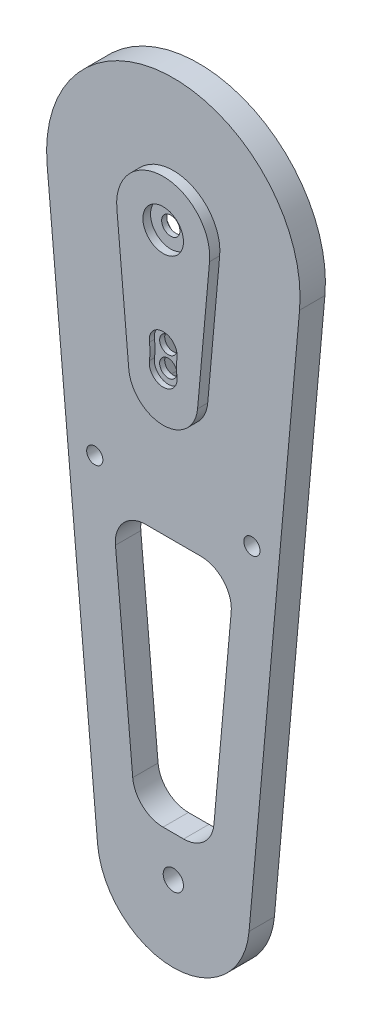
SolidWorks part; units mm, degrees
material "PLA"
ref_plane "Alzado" through (0, 0, 0) normal (0, 0, 1) x (1, 0, 0)
ref_plane "Planta" through (0, 0, 0) normal (0, 1, 0) x (1, 0, 0)
ref_plane "Vista lateral" through (0, 0, 0) normal (1, 0, 0) x (0, 0, -1)
other "PLA"
sketch "Croquis1" plane through (0, 0, 0) normal (0, 0, 1) x (1, 0, 0)
  line L0 (0, 112) -> (0, 0) construction
  line L1 (-14.9401, -1.3393) -> (-25.1002, 112)
  line L2 (14.9401, -1.3393) -> (24.9002, 109.7679)
  line L3 (0, 119.505) -> (19.4147, 119.505) construction
  line L4 (-3.55, 83.055) -> (-3.55, 100.9175)
  line L5 (3.55, 83.055) -> (3.55, 100.9175)
  line L11 (0, 112) -> (0, 123.4883) construction
  line L12 (0.5, 119.4883) -> (0.5, 119.505)
  arc A0 (-14.9401, -1.3393) -> (14.9401, -1.3393) centre (0, 0) ccw
  arc A1 (24.9002, 109.7679) -> (-24.9002, 109.7679) centre (0, 112) ccw
  circle A2 centre (0, 112) radius 7.505
  circle A3 centre (0, 0) radius 2
  circle A4 centre (0, 112) radius 1.65
  arc A5 (0, 79.505) -> (-3.55, 83.055) centre (0, 83.055) cw
  arc A6 (-5.8094, 107.2485) -> (-3.55, 100.9175) centre (-13.55, 100.9175) cw
  arc A7 (5.8094, 107.2485) -> (3.55, 100.9175) centre (13.55, 100.9175) ccw
  arc A8 (0, 79.505) -> (3.55, 83.055) centre (0, 83.055) ccw
  point P26 (0, 79.4404)
  dimension "D1" = 30
  dimension "D2" = 50
  dimension "D4" = 15.01
  dimension "D5" = 4
  dimension "D6" = 3.3
  dimension "D7" = 10
  dimension "D3" = 112
  dimension "D8" = 40
  dimension "D9" = 7.1
extrude "Saliente-Extruir1" add sketch "Croquis1" along normal blind 5 contours L2 A1 L1 A0 A2 A3 | A0 region at (0, 64.8855, 0)
ref_plane "Plano1" through (0, 0, 0) normal (1, 0, 0) x (0, -1, 0)
sketch "Croquis11" plane through (0, 0, 0) normal (0, 0, -1) x (-1, 0, 0)
  line L2 (0, 0) -> (0, 137) construction
  line L3 (-10.6804, 11.0037) -> (-15.5, 64.7681) construction
  line L4 (-14.9401, -1.3393) -> (-24.9002, 109.7679) construction
  arc A2 (24.9002, 109.7679) -> (-24.9002, 109.7679) centre (0, 112) ccw construction
  circle A3 centre (-15.5, 64.7681) radius 1.6
  circle A4 centre (15.5, 64.7681) radius 1.6
  dimension "D1" = 31
extrude "Cortar-Extruir1" cut sketch "Croquis11" against normal blind 6 contours A3 | A4
sketch "Croquis12" plane through (0, 0, 5) normal (0, 0, 1) x (1, 0, 0)
  line L0 (0, 79.5266) -> (0, 0) construction
  line L1 (-12, 58) -> (12, 58)
  line L2 (12, 58) -> (7.5178, 8)
  line L3 (7.5178, 8) -> (-7.5178, 8)
  line L4 (-12, 58) -> (-7.5178, 8)
  line L5 (14.9401, -1.3393) -> (24.9002, 109.7679) construction
  point P8 (0, 8)
  point P9 (0, 58)
  dimension "D1" = 24
  dimension "D2" = 50
  dimension "D3" = 8
extrude "Cortar-Extruir2" cut sketch "Croquis12" against normal up to next contours L4 | L0 L3 | L0 L3 | L2 | L1 L0 | L0 L1 region at (0, 34.9137, 5)
sketch "Croquis13" plane through (0, 0, 5) normal (0, 0, 1) x (1, 0, 0)
  line L0 (0, 137) -> (0, -15) construction
  line L2 (6.7847, 84.8645) -> (9.1438, 111.1803)
  line L3 (-6.7847, 84.8645) -> (-9.1438, 111.1803)
  line L4 (14.9401, -1.3393) -> (24.9002, 109.7679) construction
  arc A0 (-9.1438, 111.1803) -> (9.1438, 111.1803) centre (0, 112) ccw
  arc A2 (24.9002, 109.7679) -> (-24.9002, 109.7679) centre (0, 112) ccw construction
  arc A3 (-14.9401, -1.3393) -> (14.9401, -1.3393) centre (0, 0) ccw construction
  arc A4 (-9.1438, 111.1803) -> (9.1438, 111.1803) centre (0, 112) cw
  arc A5 (5.8094, 107.2485) -> (-5.8094, 107.2485) centre (0, 112) ccw construction
  arc A6 (6.7847, 84.8645) -> (-6.7847, 84.8645) centre (0, 85.4727) cw
  circle A7 centre (0, 112) radius 4
  circle A8 centre (0, 112) radius 1.8
  dimension "D1" = 8
  dimension "D2" = 3.6
extrude "Saliente-Extruir2" add sketch "Croquis13" along normal blind 2 contours A6 L3 A4 L2 | A8
extrude "Saliente-Extruir3" add sketch "Croquis13<3>" against normal blind 0.5 contours L0 A7 | A7 | A8 region at (-3.8869, 112, 5)
sketch "Croquis13<3>" plane through (0, 0, 5) normal (0, 0, 1) x (1, 0, 0) same geometry as "Croquis13"
sketch "Croquis14" plane through (0, 0, 7) normal (0, 0, 1) x (1, 0, 0)
  circle A0 centre (0, 112) radius 4
  dimension "D1" = 8
extrude "Cortar-Extruir3" cut sketch "Croquis14" against normal blind 1.5
chamfer "Chaflán1" distance 0.5 angle 45 6 edges at (0, 79.505, 0) (-3.55, 91.9862, 0) (3.55, 91.9862, 0) (4.1318, 104.2785, 0) (-4.1318, 104.2785, 0) (0, 119.505, 0)
sketch "Croquis15" plane through (0, 0, 5) normal (0, 0, -1) x (-1, 0, 0)
  line L0 (0, 137) -> (0, -15) construction
  arc A0 (24.9002, 109.7679) -> (-24.9002, 109.7679) centre (0, 112) ccw construction
  arc A1 (-14.9401, -1.3393) -> (14.9401, -1.3393) centre (0, 0) ccw construction
  circle A2 centre (0, 87.915) radius 1.45
  circle A3 centre (0, 91.915) radius 1.45
  arc A4 (-3.55, 83.055) -> (3.55, 83.055) centre (0, 83.055) ccw construction
  circle A5 centre (0, 91.915) radius 0.75
  circle A6 centre (0, 87.915) radius 0.75
  point P15 (0, 79.505)
  dimension "D1" = 8.41
  dimension "D3" = 2.9
  dimension "D4" = 1.5
  dimension "D2" = 4
hole_wizard "Refrentado para tornillo con cabeza troncocónica de M31" positions "Croquis16" profile "Croquis17" counterbore size "M3" standard "Ansi Metric" end condition up to next
sketch "Croquis16" plane through (0, 0, 7) normal (0, 0, -1) x (-1, 0, 0)
  point P0 (0, 91.915)
  point P3 (0, 87.915)
sketch "Croquis17" plane through (0, 91.915, 7) normal (1, 0, 0) x (0, -1, 0)
  line L0 (0, 0) -> (0, 2)
  line L1 (0, 2) -> (1.7, 2)
  line L3 (1.7, 2) -> (1.7, 1)
  line L4 (1.7, 1) -> (2.75, 1)
  line L5 (2.75, 1) -> (2.75, 0)
  line L7 (2.75, 0) -> (0, 0)
  line L11 (0, -6.35) -> (0, 107.95) construction
  dimension "Diámetro de taladro hasta el siguiente" = 3.4
  dimension "Profundidad de taladro hasta el siguiente" = 2
  dimension "Diámetro de refrentado" = 5.5
  dimension "Profundidad de refrentado" = 1
fillet "Redondeo1" radius 10 2 edges at (-1.8875, 89.915, 6.5) (1.8875, 89.915, 6.5)
fillet "Redondeo2" radius 6 4 edges at (7.5178, 8, 2.5) (-7.5178, 8, 2.5) (12, 58, 2.5) (-12, 58, 2.5)
